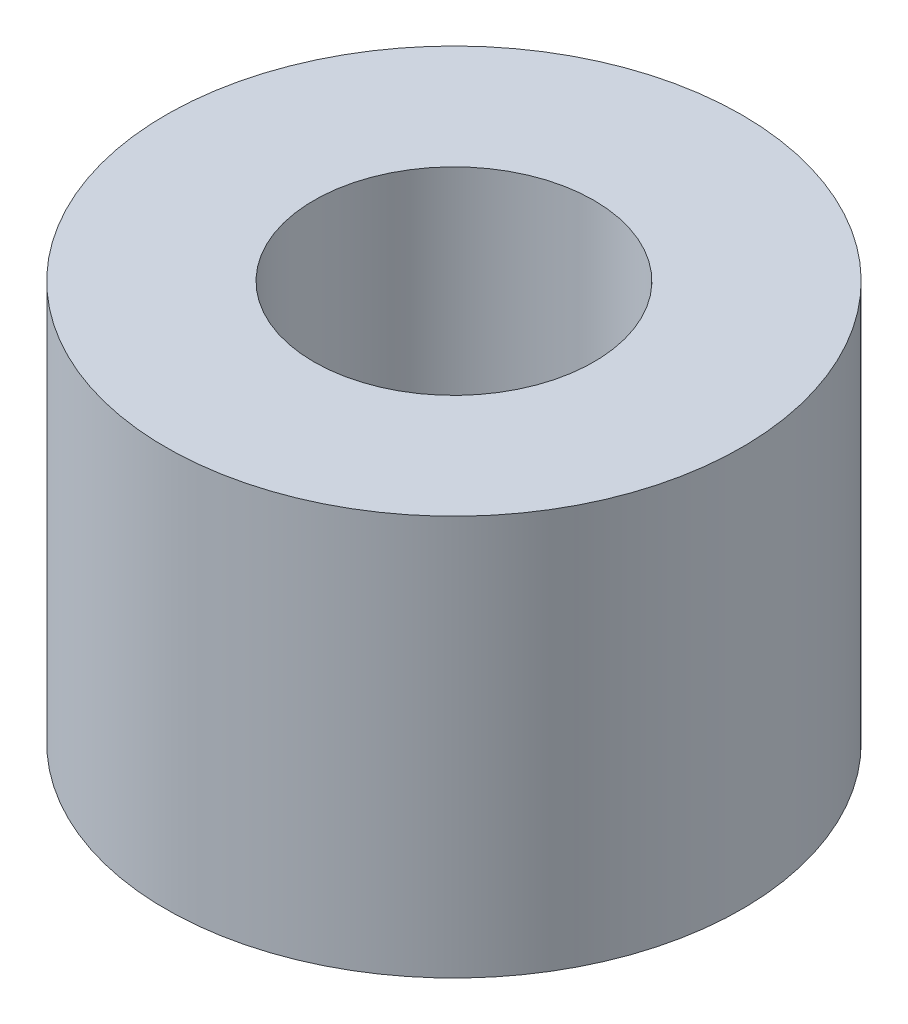
SolidWorks part; units mm, degrees
ref_plane "Front Plane" through (0, 0, 0) normal (0, 0, 1) x (1, 0, 0)
ref_plane "Top Plane" through (0, 0, 0) normal (0, 1, 0) x (1, 0, 0)
ref_plane "Right Plane" through (0, 0, 0) normal (1, 0, 0) x (0, 0, -1)
ref_plane "Plane1"
sketch "Sketch1" plane through (0, 0, 0) normal (0, 1, 0) x (-1, 0, 0)
  circle A0 centre (0, 0) radius 4.572
  circle A1 centre (0, 0) radius 2.2225
  dimension "D1" = 4.445
  dimension "D2" = 9.144
extrude "Extrusion1" add sketch "Sketch1" along normal blind 6.35 contours A0 A1 region at (4.4427, 0, 0)
